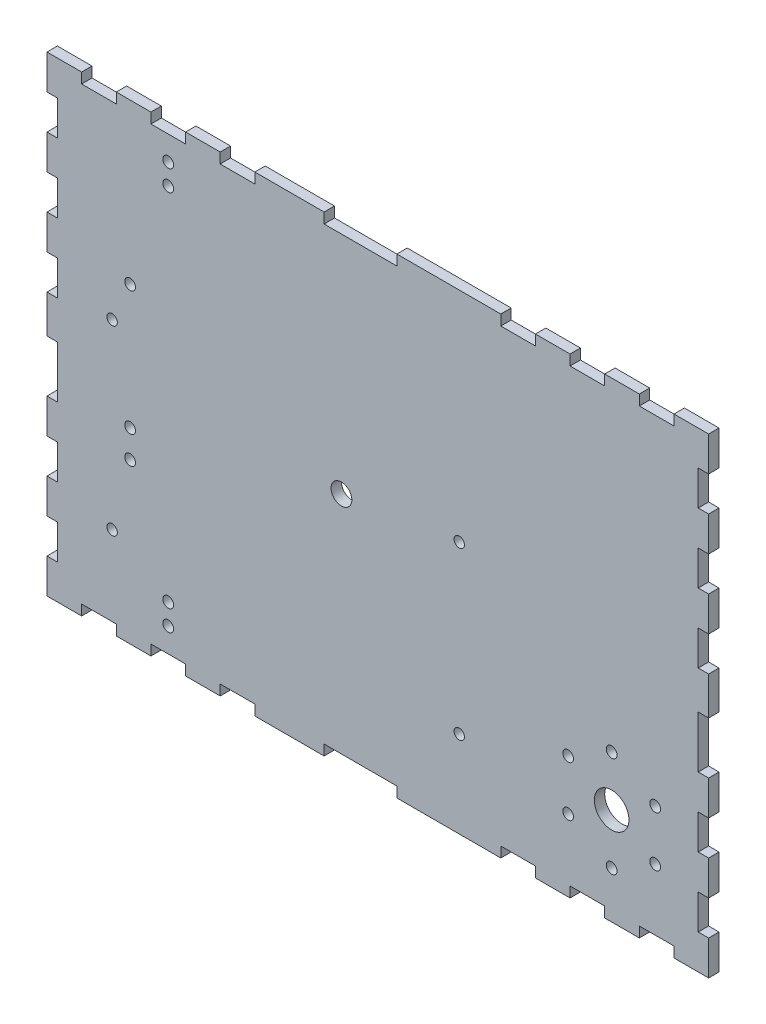
SolidWorks part; units mm, degrees
note: '?' marks a value the reader was unsure of.
ref_plane "Front Plane" through (0, 0, 0) normal (0, 0, 1) x (1, 0, 0)
ref_plane "Top Plane" through (0, 0, 0) normal (0, 1, 0) x (1, 0, 0)
ref_plane "Right Plane" through (0, 0, 0) normal (1, 0, 0) x (0, 0, -1)
sketch "Sketch2" plane through (0, 0, 0) normal (0, 0, 1) x (1, 0, 0)
  line L1 (0, 0) -> (191, 0)
  line L2 (0, 0) -> (0, 136)
  line L3 (0, 136) -> (191, 136)
  line L4 (191, 0) -> (191, 136)
  circle A0 centre (35, 16) radius 1.55 construction
  circle A1 centre (35, 10) radius 1.55 construction
  circle A2 centre (24, 46.0692) radius 1.55 construction
  circle A3 centre (24, 54.0692) radius 1.55 construction
  circle A5 centre (24, 89.9308) radius 1.55 construction
  circle A6 centre (35, 120) radius 1.55 construction
  circle A7 centre (35, 126) radius 1.55 construction
  circle A8 centre (175.5574, 35.25) radius 1.55 construction
  circle A9 centre (163, 42.5) radius 1.55 construction
  circle A10 centre (150.4426, 35.25) radius 1.55 construction
  circle A11 centre (150.4426, 20.75) radius 1.55 construction
  circle A12 centre (163, 13.5) radius 1.55 construction
  circle A13 centre (175.5574, 20.75) radius 1.55 construction
  circle A14 centre (35, 16) radius 1.55
  circle A15 centre (35, 10) radius 1.55
  circle A16 centre (24, 46.0692) radius 1.55
  circle A17 centre (24, 54.0692) radius 1.55
  circle A18 centre (18.8, 26) radius 1.5 construction
  circle A19 centre (24, 89.9308) radius 1.55
  circle A20 centre (35, 120) radius 1.55
  circle A21 centre (35, 126) radius 1.55
  circle A22 centre (175.5574, 35.25) radius 1.55
  circle A23 centre (163, 42.5) radius 1.55
  circle A24 centre (150.4426, 35.25) radius 1.55
  circle A25 centre (150.4426, 20.75) radius 1.55
  circle A26 centre (163, 13.5) radius 1.55
  circle A27 centre (175.5574, 20.75) radius 1.55
  circle A28 centre (18.8, 78.5) radius 1.5 construction
  circle A29 centre (18.8, 78.5) radius 1.5
  circle A30 centre (119, 73) radius 1.5 construction
  circle A31 centre (119, 25) radius 1.5 construction
  circle A32 centre (18.8, 26) radius 1.5
  circle A33 centre (119, 73) radius 1.5
  circle A34 centre (119, 25) radius 1.5
extrude "Boss-Extrude1" add sketch "Sketch2" along normal blind 3
ref_axis "Axis1" through (0, 68, 3) along (1, 0, 0)?
ref_plane "Plane1" through (0, 68, 0) normal (0, 1, 0) x (1, 0, 0)
ref_axis "Axis2" through (95.5, 0, 3) along (0, 1, 0)?
ref_plane "Plane2" through (95.5, 0, 0) normal (1, 0, 0) x (0, 0, -1)
sketch "Sketch3" plane through (0, 0, 3) normal (0, 0, 1) x (1, 0, 0)
  line L0 (0, 3) -> (191, 3) construction
  line L1 (0, 136) -> (0, 0) construction
  line L2 (191, 0) -> (191, 136) construction
  line L3 (0, 0) -> (191, 0) construction
  line L4 (10, 0) -> (10, 3)
  line L5 (20, 0) -> (20, 3)
  line L6 (30, 0) -> (30, 3)
  line L7 (40, 0) -> (40, 3)
  line L8 (50, 0) -> (50, 3)
  line L9 (60, 0) -> (60, 3)
  line L10 (10, 0) -> (20, 0)
  line L11 (20, 3) -> (10, 3)
  line L12 (30, 0) -> (40, 0)
  line L13 (40, 3) -> (30, 3)
  line L14 (50, 0) -> (60, 0)
  line L15 (80, 3) -> (80, 0)
  line L16 (60, 3) -> (50, 3)
  line L17 (181, 0) -> (181, 3)
  line L18 (171, 0) -> (171, 3)
  line L19 (161, 0) -> (161, 3)
  line L20 (151, 0) -> (151, 3)
  line L21 (141, 0) -> (141, 3)
  line L22 (131, 0) -> (131, 3)
  line L23 (181, 0) -> (171, 0)
  line L24 (171, 0) -> (170.9794, -0.0476)
  line L25 (171, 3) -> (181, 3)
  line L26 (181, 3) -> (181.0353, 3.2173)
  line L27 (161, 0) -> (151, 0)
  line L28 (161, 3) -> (151, 3)
  line L29 (141, 0) -> (131, 0)
  line L30 (131, 3) -> (141, 3)
  line L31 (141, 3) -> (140.9859, 2.9583)
  line L32 (101, 0) -> (101, 3)
  line L33 (80, 0) -> (101, 0)
  line L34 (101, 3) -> (80, 3)
  dimension "D6" = 20
  dimension "D1" = 3
  dimension "D2" = 10
  dimension "D4" = 10
  dimension "D7" = 30
  dimension "D3" = 6
  dimension "D5" = 6
extrude "Cut-Extrude1" cut sketch "Sketch3" against normal up to next
mirror "Mirror1" about plane through (0, 68, 0) normal (0, 1, 0) of "Cut-Extrude1"
sketch "Sketch4" plane through (0, 0, 3) normal (0, 0, 1) x (1, 0, 0)
  line L0 (3, 136) -> (3, 0) construction
  line L1 (10, 136) -> (0, 136) construction
  line L2 (0, 0) -> (10, 0) construction
  line L3 (0, 136) -> (0, 0) construction
  line L4 (0, 126) -> (3, 126)
  line L5 (0, 116) -> (3, 116)
  line L6 (0, 106) -> (3, 106)
  line L7 (0, 96) -> (3, 96)
  line L8 (0, 86) -> (3, 86)
  line L9 (0, 10) -> (3, 10)
  line L10 (0, 20) -> (3, 20)
  line L11 (0, 30) -> (3, 30)
  line L12 (0, 40) -> (3, 40)
  line L13 (0, 50) -> (3, 50)
  line L14 (0, 126) -> (0, 116)
  line L15 (3, 116) -> (3, 126)
  line L16 (0, 106) -> (0, 96)
  line L17 (3, 96) -> (3, 106)
  line L18 (0, 20) -> (0, 10)
  line L19 (3, 10) -> (3, 20)
  line L20 (0, 30) -> (0, 40)
  line L21 (3, 30) -> (3, 40)
  line L22 (0, 65) -> (3, 65)
  line L23 (0, 76) -> (3, 76)
  line L24 (0, 86) -> (0, 76)
  line L25 (3, 76) -> (3, 86)
  line L26 (0, 65) -> (0, 50)
  line L27 (3, 50) -> (3, 65)
  dimension "D1" = 3
  dimension "D2" = 10
  dimension "D4" = 10
  dimension "D6" = 15
  dimension "D3" = 6
  dimension "D5" = 5
extrude "Cut-Extrude2" cut sketch "Sketch4" against normal up to next
mirror "Mirror2" about plane through (95.5, 0, 0) normal (1, 0, 0) of "Cut-Extrude2"
sketch "Sketch6" plane through (0, 0, 3) normal (0, 0, 1) x (1, 0, 0)
  line L0 (116, 0) -> (116, 136) construction
  line L1 (101, 0) -> (131, 0) construction
  line L2 (131, 136) -> (101, 136) construction
  line L3 (191, 68) -> (85, 68) construction
  line L4 (191, 65) -> (191, 76) construction
  dimension "D1" = 106
ref_point "MountPoint-Dif"
sketch "Sketch8" plane through (0, 0, 0) normal (0, 0, -1) x (-1, 0, 0)
  circle A0 centre (-163, 28) radius 8 construction
  circle A1 centre (-163, 28) radius 8
  circle A2 centre (-163, 28) radius 5
  dimension "D1" = 10
extrude "Cut-Extrude3" cut sketch "Sketch8" against normal up to next contours A2
sketch "Sketch9" plane through (0, 0, 3) normal (0, 0, 1) x (1, 0, 0)
  circle A0 centre (85, 68) radius 3
  point P0 (85, 68)
  dimension "D1" = 6
extrude "Cut-Extrude4" cut sketch "Sketch9" against normal up to next
